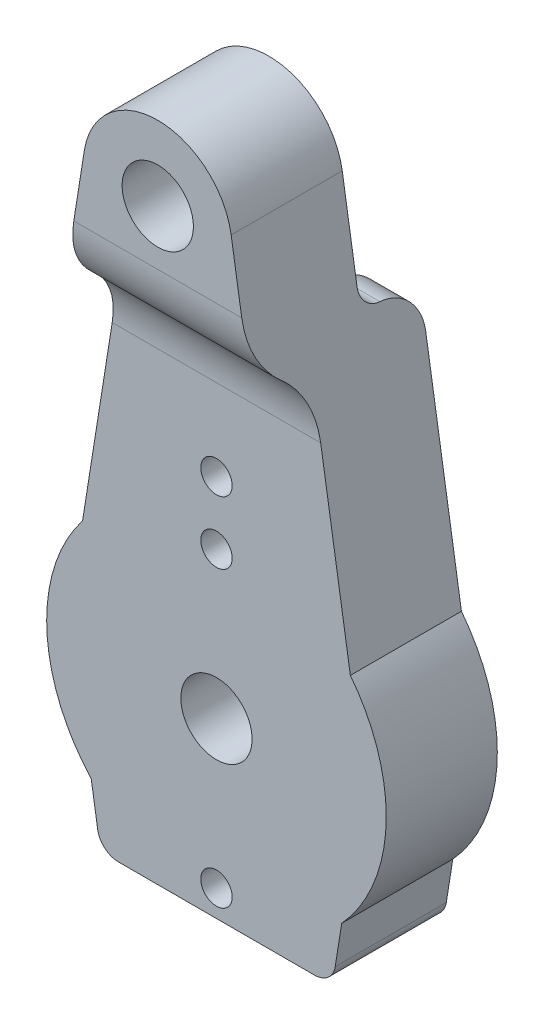
SolidWorks part; units mm, degrees
material "PLA 100% Infill"
ref_plane "Front Plane" through (0, 0, 0) normal (0, 0, 1) x (1, 0, 0)
ref_plane "Top Plane" through (0, 0, 0) normal (0, 1, 0) x (1, 0, 0)
ref_plane "Right Plane" through (0, 0, 0) normal (1, 0, 0) x (0, 0, -1)
sketch "Sketch1" plane through (0, 0, 0) normal (0, 0, 1) x (1, 0, 0)
  line L2 (-4.2619, 18.3531) -> (4.2619, 18.3531)
  line L3 (-2.469, 16.8925) -> (-2.2368, 18.3531) construction
  line L9 (2.469, 16.8925) -> (2.2368, 18.3531) construction
  line L10 (-4.5, 4.1183) -> (-4.5, 10.6021)
  line L11 (-4.5, 10.6021) -> (-3.4691, 10.6021) construction
  line L14 (0, -8.2602) -> (0, 19) construction
  line L15 (6.3881, 4.9802) -> (4.4442, 17.2066)
  line L16 (6.3881, 4.9802) -> (4.4442, 17.2066)
  line L17 (5.9754, -5.4685) -> (5.5315, -8.2602)
  line L18 (5.5315, -8.2602) -> (-5.5315, -8.2602)
  line L19 (2.469, -16.8925) -> (4.5, -4.1183) construction
  line L20 (4.4442, 17.2066) -> (3.5013, 23.1367)
  line L21 (0, 19) -> (0, 33.2339) construction
  line L22 (-4.4442, 17.2066) -> (-3.5013, 23.1367)
  line L23 (-6.3881, 4.9802) -> (-4.4442, 17.2066)
  line L24 (-5.9754, -5.4685) -> (-5.5315, -8.2602)
  line L25 (2.469, 16.8925) -> (4.5, 4.1183) construction
  line L26 (-2.469, 16.8925) -> (-4.5, 4.1183) construction
  line L27 (-2.469, -16.8925) -> (-4.5, -4.1183) construction
  line L28 (3.8415, -8.2602) -> (4.5, -4.1183) construction
  line L29 (2.469, 16.8925) -> (4.5, 4.1183) construction
  line L30 (-2.469, 16.8925) -> (-4.5, 4.1183) construction
  line L31 (-3.8415, -8.2602) -> (-4.5, -4.1183) construction
  line L32 (4.5, 10.6021) -> (4.5, 4.1183)
  line L33 (3.4691, 10.6021) -> (4.5, 10.6021) construction
  line L34 (-2.2368, 18.3531) -> (-4.5, 10.6021)
  line L35 (2.2368, 18.3531) -> (4.5, 10.6021)
  line L36 (-4.5, -4.1183) -> (-4.5, -8.2602)
  line L38 (4.5, -8.2602) -> (4.5, -4.1183)
  arc A2 (-5.9754, -5.4685) -> (-6.3881, 4.9802) centre (0, 0) cw
  arc A3 (2.2368, 18.3531) -> (-2.2368, 18.3531) centre (0, 17.7) ccw
  circle A6 centre (0, 0) radius 1.6
  arc A10 (3.5013, 23.1367) -> (-3.5013, 23.1367) centre (0, 22.58) ccw
  arc A13 (5.9754, -5.4685) -> (6.3881, 4.9802) centre (0, 0) ccw
  arc A14 (5.9754, -5.4685) -> (6.3881, 4.9802) centre (0, 0) ccw
  arc A15 (2.469, 16.8925) -> (-2.469, 16.8925) centre (0, 16.5) ccw construction
  circle A16 centre (0, 22.58) radius 1.7
  circle A17 centre (0, 16) radius 0.75 construction
  circle A18 centre (0, 13) radius 0.75 construction
  circle A19 centre (0, 10) radius 0.75 construction
  circle A20 centre (0, 7) radius 0.75 construction
  circle A21 centre (0, -7) radius 0.75 construction
  circle A22 centre (0, 16) radius 0.75
  circle A23 centre (0, 13) radius 0.75
  circle A24 centre (0, 10) radius 0.75
  circle A25 centre (0, 7) radius 0.75
  circle A26 centre (0, -7) radius 0.75
  arc A27 (4.5, -4.1183) -> (4.5, 4.1183) centre (0, 0) ccw construction
  arc A28 (-4.5, 4.1183) -> (-4.5, -4.1183) centre (0, 0) ccw construction
  arc A29 (4.5, -4.1183) -> (4.5, 4.1183) centre (0, 0) ccw
  arc A30 (2.469, 16.8925) -> (-2.469, 16.8925) centre (0, 16.5) ccw construction
  arc A31 (-4.5, 4.1183) -> (-4.5, -4.1183) centre (0, 0) ccw
  point P24 (0, -8.2602)
  arc M60 (4.5, -4.1183) -> (4.5, 4.1183) centre (0, 0) ccw
  line M61 (4.5, 4.1183) -> (2.469, 16.8925)
  arc M62 (2.469, 16.8925) -> (-2.469, 16.8925) centre (0, 16.5) ccw
  line M63 (-2.469, 16.8925) -> (-4.5, 4.1183)
  arc M64 (-4.5, 4.1183) -> (-4.5, -4.1183) centre (0, 0) ccw
  line M65 (-4.5, -4.1183) -> (-2.469, -16.8925)
  line M67 (2.469, -16.8925) -> (4.5, -4.1183)
  circle M68 centre (0, 0) radius 1.5
  circle M69 centre (0, 7) radius 0.75
  circle M70 centre (0, 10) radius 0.75
  circle M71 centre (0, 13) radius 0.75
  circle M72 centre (0, 16) radius 0.75
  circle M73 centre (0, -7) radius 0.75
  circle M74 centre (0, -10) radius 0.75
  dimension "D2" = 2
  dimension "D4" = 3.4
  dimension "D5" = 2.3302
  dimension "D6" = 22.58
  dimension "D8" = 3.2
  dimension "D1" = 2.8268
  dimension "D3" = 6.4838
extrude "Boss-Extrude4" add sketch "Sketch1" against normal blind 2.3 contours A30 L20 A10 L22 A16 | A31 L30 A30 L23 A2 L24 L18 L31 | A30 L29 A29 L28 L18 L17 A14 L16 region at (-3.7677, 20.7268, 0) region at (-5.4944, 4.5544, 0) region at (5.4944, 4.5544, 0)
extrude "Boss-Extrude6" add sketch "Sketch1<9>" along normal blind 3 and the other way blind 0.1 contours A2 L24 L18 L36 L10 L34 L2 L22 L23 M64 | L2 A3 | L35 L2 L34 L10 L32 M63 M62 M61 | L18 M67 M60 M61 M62 M63 M64 M65 M74 M68 M70 M72 M73 M71 M69 | L17 A14 L16 L20 L2 L35 L32 L38 L18 M60 | L18 L38 M67 | L36 L18 M65 | L35 L2 L32 M62 M61 | L2 M62 | A16 | A25 | A24 | A26 | A2 L23 L22 A10 L20 L16 A14 L17 L18 L24 region at (-5.4944, 4.5544, 0) region at (0, 19.2108, 0) region at (-3.6924, 11.2543, 0) region at (0, 18.615, 0) region at (0, 3.4642, 0) region at (3.6924, 11.2543, 0) region at (5.4944, 4.5544, 0) region at (-4.2805, -6.8796, 0) region at (4.2805, -6.8796, 0) region at (0, 22.58, 0)
sketch "Sketch1<9>" plane through (0, 0, 0) normal (0, 0, 1) x (1, 0, 0) same geometry as "Sketch1"
fillet "Fillet2" radius 1 2 edges at (5.5315, -8.2602, 0.35) (-5.5315, -8.2602, 0.35)
sketch "Sketch2" plane through (0, 0, -0.1) normal (0, 0, -1) x (-1, 0, 0)
  circle A0 centre (0, 0) radius 1.7
  dimension "D1" = 3.4
extrude "Cut-Extrude1" cut sketch "Sketch2" against normal through all
sketch "Sketch3" plane through (0, 0, 3) normal (0, 0, 1) x (1, 0, 0)
  circle A0 centre (0, 0) radius 3
  dimension "D1" = 6
extrude "Cut-Extrude2" [suppressed] cut sketch "Sketch3" against normal blind 1
sketch "Sketch7" plane through (0, 0, -2.3) normal (0, 0, -1) x (-1, 0, 0)
  line L0 (6.3881, 4.9802) -> (3.5013, 23.1367) construction
  line L1 (4.3657, 17.7) -> (3.5013, 23.1367)
  line L2 (-6.3881, 4.9802) -> (-3.5013, 23.1367) construction
  line L3 (-4.3657, 17.7) -> (-3.5013, 23.1367)
  line L4 (4.3657, 17.7) -> (-4.3657, 17.7)
  arc A0 (3.5013, 23.1367) -> (-3.5013, 23.1367) centre (0, 22.58) ccw construction
  arc A1 (3.5013, 23.1367) -> (-3.5013, 23.1367) centre (0, 22.58) ccw
  circle A4 centre (0, 22.58) radius 1.7 construction
  circle A5 centre (0, 22.58) radius 1.7
  point P7 (0, 17.7)
extrude "Cut-Extrude4" cut sketch "Sketch7" against normal blind 2.8
fillet "Fillet3" radius 2 1 edges at (-3.3966, 17.7, -2.3)
fillet "Fillet4" radius 1 1 edges at (0, 17.7, 0.5)
sketch "Sketch8" plane through (0, 0, 3) normal (0, 0, 1) x (1, 0, 0)
  line L0 (-4.3664, 17.6956) -> (-2.4288, 17.6956) construction
  line L1 (-4.2078, 18.6933) -> (-4.3664, 17.6956) construction
  line L2 (-4.2078, 18.6933) -> (-3.5013, 23.1367) construction
  line L3 (3.5013, 23.1367) -> (4.2078, 18.6933) construction
  line L4 (4.3664, 17.6956) -> (4.2078, 18.6933) construction
  line L5 (2.4288, 17.6956) -> (4.3664, 17.6956) construction
  line L6 (-4.3664, 17.6956) -> (-2.4288, 17.6956)
  line L7 (-4.2078, 18.6933) -> (-4.3664, 17.6956)
  line L8 (-4.2078, 18.6933) -> (-3.5013, 23.1367)
  line L9 (3.5013, 23.1367) -> (4.2078, 18.6933)
  line L10 (4.3664, 17.6956) -> (4.2078, 18.6933)
  line L11 (2.4288, 17.6956) -> (4.3664, 17.6956)
  line L12 (2.4288, 17.6956) -> (-2.4288, 17.6956)
  arc A0 (3.5013, 23.1367) -> (-3.5013, 23.1367) centre (0, 22.58) ccw construction
  arc A1 (3.5013, 23.1367) -> (-3.5013, 23.1367) centre (0, 22.58) ccw
  circle A2 centre (0, 22.58) radius 1.7 construction
  circle A3 centre (0, 22.58) radius 1.7
extrude "Boss-Extrude7" add sketch "Sketch8" along normal blind 2.8
fillet "Fillet5" radius 4 1 edges at (0, 17.6956, 3)
fillet "Fillet6" radius 4 1 edges at (0, 17.6956, 5.8)
